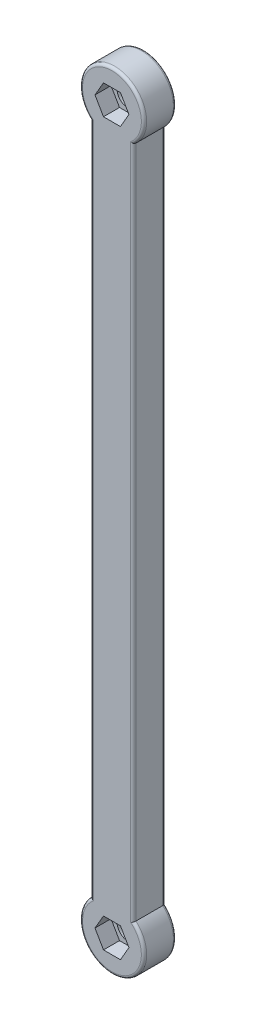
SolidWorks part; units mm, degrees
ref_plane "前视基准面" through (0, 0, 0) normal (0, 0, 1) x (1, 0, 0)
ref_plane "上视基准面" through (0, 0, 0) normal (0, 1, 0) x (1, 0, 0)
ref_plane "右视基准面" through (0, 0, 0) normal (1, 0, 0) x (0, 0, -1)
other "Configuration Table"
sketch "草图1" plane through (0, 0, 0) normal (0, 0, 1) x (1, 0, 0)
  line L0 (0, 0) -> (0, 135) construction
  line L1 (-4, 130.5279) -> (-4, 4.4721)
  line L2 (4, 130.5279) -> (4, 4.4721)
  line L3 (-4, 130.5279) -> (4, 130.5279) construction
  line L4 (-4, 4.4721) -> (4, 4.4721) construction
  arc A0 (4, 130.5279) -> (-4, 130.5279) centre (0, 135) ccw
  arc A1 (-4, 4.4721) -> (4, 4.4721) centre (0, 0) ccw
  circle A2 centre (0, 135) radius 2.05
  circle A3 centre (0, 0) radius 2.05
  point P10 (0, 4.4721)
  dimension "D2" = 6
  dimension "D4" = 4.1
  dimension "D5" = 4.1
  dimension "D1" = 135
  dimension "D3" = 8
extrude "凸台-拉伸1" add sketch "草图1" along normal mid plane 6 contours L1 A1 L2 A0 A3 A2 region at (0, 67.5, 0)
ref_axis "下旋转基准轴" through (0, 0, 0) along (0, 0, 1)
ref_axis "上旋转基准轴" through (0, 135, 0) along (0, 0, 1)
sketch "草图2" plane through (0, 0, 3) normal (0, 0, 1) x (1, 0, 0)
  line L1 (1.5877, -2.75) -> (3.1754, 0)
  line L2 (3.1754, 0) -> (1.5877, 2.75)
  line L3 (1.5877, 2.75) -> (-1.5877, 2.75)
  line L4 (-1.5877, 2.75) -> (-3.1754, 0)
  line L5 (-3.1754, 0) -> (-1.5877, -2.75)
  line L6 (-1.5877, -2.75) -> (1.5877, -2.75)
  line L7 (1.5877, 132.25) -> (3.1754, 135)
  line L8 (3.1754, 135) -> (1.5877, 137.75)
  line L9 (1.5877, 137.75) -> (-1.5877, 137.75)
  line L10 (-1.5877, 137.75) -> (-3.1754, 135)
  line L11 (-3.1754, 135) -> (-1.5877, 132.25)
  line L12 (-1.5877, 132.25) -> (1.5877, 132.25)
  circle A0 centre (0, 0) radius 2.75 construction
  circle A1 centre (0, 135) radius 2.75 construction
  dimension "D1" = 5.5
  dimension "D2" = 5.5
extrude "切除-拉伸1" cut sketch "草图2" against normal blind 3
fillet "圆角1" radius 0.5 8 edges at (0, -6, 3) (0, -6, -3) (0, 141, 3) (0, 141, -3) (4, 67.5, -3) (4, 67.5, 3) (-4, 67.5, 3) (-4, 67.5, -3)
